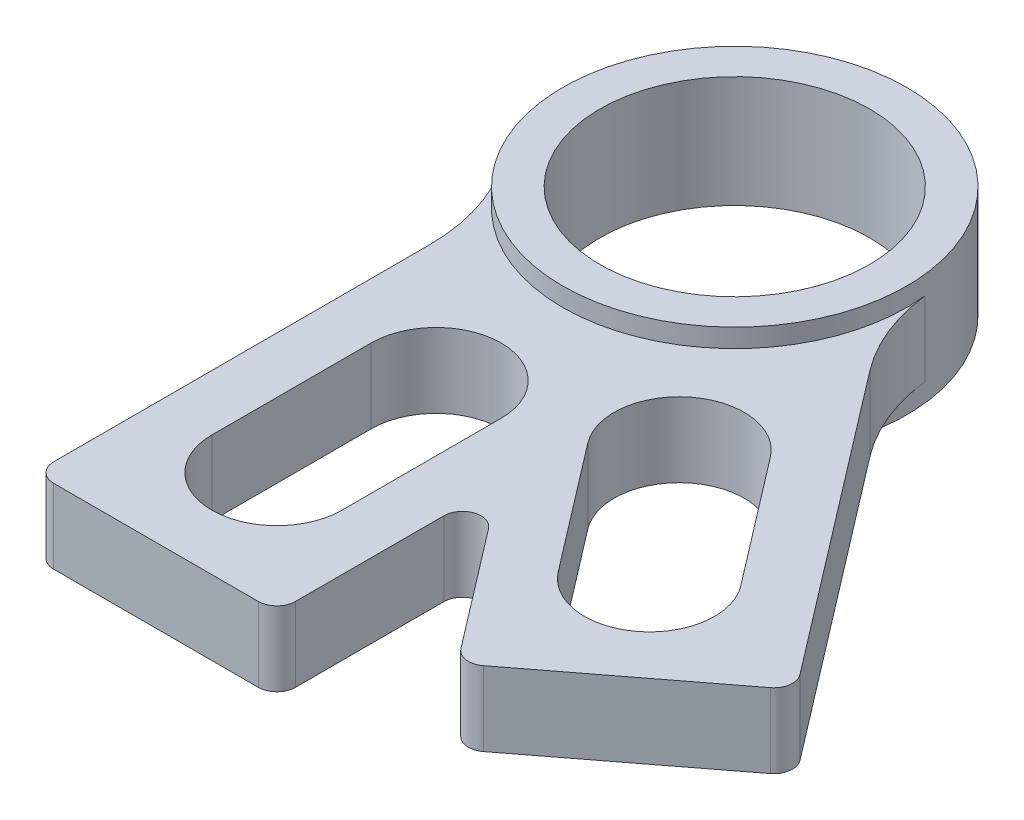
SolidWorks part; units mm, degrees
material "AISI 4130 Steel, annealed at 865C"
ref_plane "Front Plane" through (0, 0, 0) normal (0, 0, 1) x (1, 0, 0)
ref_plane "Top Plane" through (0, 0, 0) normal (0, 1, 0) x (1, 0, 0)
ref_plane "Right Plane" through (0, 0, 0) normal (1, 0, 0) x (0, 0, -1)
sketch "Sketch1" plane through (0, 0, 0) normal (0, 1, 0) x (1, 0, 0)
  line L0 (0, 0) -> (0, -49.3903) construction
  line L1 (0, 0) -> (30.021, -39.2192) construction
  line L2 (0, -39.0716) -> (0, -25.4826) construction
  line L3 (-5.5562, -39.0716) -> (-5.5562, -25.4826)
  line L4 (5.5563, -39.0716) -> (5.5563, -25.4826)
  line L5 (23.7489, -31.0254) -> (15.4891, -20.2348) construction
  line L6 (19.3369, -34.4027) -> (11.0771, -23.6121)
  line L7 (28.1609, -27.6481) -> (19.9011, -16.8576)
  line L8 (0, -49.3903) -> (0, -44.6278) construction
  line L9 (30.021, -39.2192) -> (27.1262, -35.4374) construction
  line L10 (-10.3187, -49.3903) -> (10.3188, -49.3903)
  line L11 (21.8272, -45.4912) -> (38.2147, -32.9471)
  line L12 (-10.3187, -49.3903) -> (-10.3187, -10.4432)
  line L13 (10.3188, -49.3903) -> (10.3188, -30.4567)
  line L14 (38.2147, -32.9471) -> (14.5415, -2.0206)
  line L15 (21.8272, -45.4912) -> (10.3188, -30.4567)
  line L16 (176.9204, -231.1275) -> (14.2404, -18.6035) construction
  line L22 (0, 0) -> (10.3188, -30.4567) construction
  circle A0 centre (0, 0) radius 11.5062
  circle A1 centre (0, 0) radius 14.6812
  arc A2 (-5.5562, -39.0716) -> (5.5563, -39.0716) centre (0, -39.0716) ccw
  arc A3 (5.5563, -25.4826) -> (-5.5562, -25.4826) centre (0, -25.4826) ccw
  arc A4 (19.3369, -34.4027) -> (28.1609, -27.6481) centre (23.7489, -31.0254) ccw
  arc A5 (19.9011, -16.8576) -> (11.0771, -23.6121) centre (15.4891, -20.2348) ccw
  point P8 (0, -32.2771)
  point P13 (19.619, -25.6301)
  point P25 (0, -49.3903)
  point P27 (30.021, -39.2192)
  dimension "D2" = 29.3624
  dimension "D3" = 4.7625
  dimension "D4" = 4.7625
  dimension "D5" = 13.589
  dimension "D6" = 49.3903
  dimension "D7" = 20.6375
extrude "Bearing_Insert_Extrude" add sketch "Sketch1" along normal mid plane 9.525 contours A1 A0 region at (-5.4988, 0, -13.1636)
extrude "Apex_Slot_Insert_Extrude" add sketch "Sketch1<4>" along normal mid plane 6.35 contours A1 L12 L10 L13 L15 L11 L14 A5 L7 A4 L6 A3 L4 A2 L3 region at (9.7483, 0, 28.773)
sketch "Sketch1<4>" plane through (0, 0, 0) normal (0, 1, 0) x (1, 0, 0) same geometry as "Sketch1"
fillet "Fillet1" radius 16.002 2 edges at (14.5415, 0, 2.0206) (-10.3187, 0, 10.4432)
fillet "Fillet2" radius 1.5875 5 edges at (38.2147, 0, 32.9471) (21.8272, 0, 45.4912) (10.3188, 0, 30.4567) (10.3188, 0, 49.3903) (-10.3187, 0, 49.3903)
equation "\"Apex_thickness\"= .25"
equation "\"Bearing_diameter\"= 0.906in"
equation "\"A-arm_angle\"= 39.1893"
equation "\"D1@Sketch1\"=\"Bearing_diameter\""
equation "\"D1@Apex_Slot_Insert_Extrude\"=\"Apex_thickness\""
